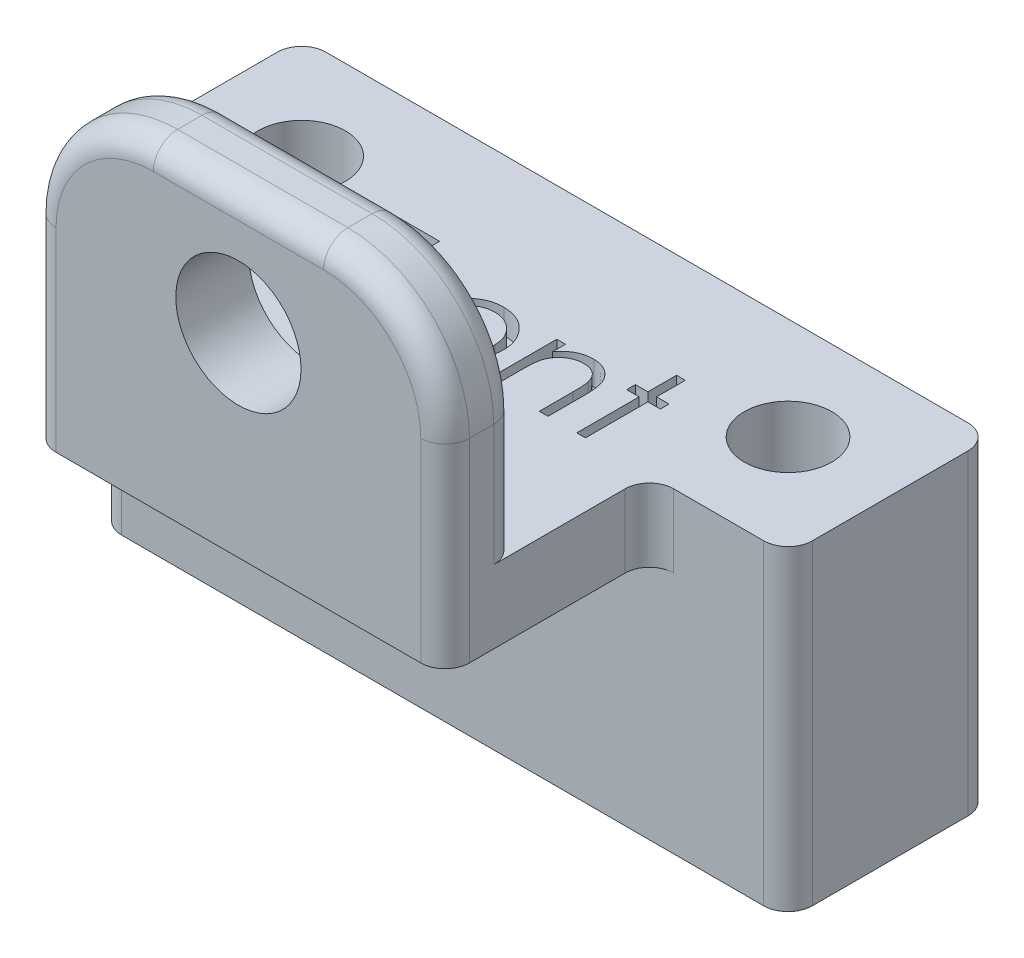
SolidWorks part; units mm, degrees
ref_plane "Front Plane" through (0, 0, 0) normal (0, 0, 1) x (1, 0, 0)
ref_plane "Top Plane" through (0, 0, 0) normal (0, 1, 0) x (1, 0, 0)
ref_plane "Right Plane" through (0, 0, 0) normal (1, 0, 0) x (0, 0, -1)
sketch "Sketch1" plane through (0, 0, 0) normal (1, 0, 0) x (0, 0, -1)
  line L0 (0, 0) -> (16.8, 0)
  line L1 (16.8, 0) -> (16.8, 3)
  line L2 (16.8, 3) -> (3, 3)
  line L3 (3, 3) -> (3, 13)
  line L4 (3, 13) -> (0, 13)
  line L5 (0, 13) -> (0, 0)
  line L6 (8.4, 3) -> (8.4, 0)
  dimension "D1" = 3
  dimension "D2" = 13
  dimension "D3" = 16.8
  dimension "D4" = 8.4
extrude "Boss-Extrude1" add sketch "Sketch1" along normal blind 17 contours L6 L2 L3 L4 L5 L0 | L2 L6 L0 L1 region at (0, 5.0326, -2.7326) region at (0, 1.5, -12.6)
extrude "Boss-Extrude3" add sketch "Sketch1<3>" against normal blind 5.7 from offset 0 contours L2 L6 L0 L1 region at (0, 1.5, -12.6)
sketch "Sketch1<3>" plane through (0, 0, 0) normal (1, 0, 0) x (0, 0, -1) same geometry as "Sketch1"
extrude "Boss-Extrude4" add sketch "Sketch1<4>" along normal blind 5.7 from surface contours L2 L6 L0 L1 region at (0, 1.5, -12.6) starting at face at (17, 5.3333, -6.6)
sketch "Sketch1<4>" plane through (0, 0, 0) normal (1, 0, 0) x (0, 0, -1) same geometry as "Sketch1"
sketch "Sketch2" plane through (0, 0, 0) normal (0, 0, 1) x (1, 0, 0)
  line L2 (8.5, 0) -> (8.5, 8) construction
  line L3 (17, 13) -> (0, 13) construction
  line L4 (17, 0) -> (0, 0) construction
  point P7 (8.5, 8)
  point P13 (8.5, 8)
  dimension "D1" = 5
hole_wizard "Ø5.0mm Dowel Hole1" positions "Sketch2" profile "Sketch3" hole size "Ø5.0" standard "ANSI Metric"
sketch "Sketch3" plane through (8.5, 8, 0) normal (1, 0, 0) x (0, -1, 0)
  line L0 (0, 0) -> (0, 4.5472)
  line L1 (0, 4.5472) -> (2.575, 3)
  line L2 (2.575, 3) -> (2.575, 0)
  line L5 (2.575, 0) -> (0, 0)
  line L10 (0, 4.5472) -> (-2.575, 3) construction
  line L11 (0, -6.35) -> (0, 107.95) construction
  dimension "Hole Dia." = 5.15
  dimension "Hole Depth" = 3
  dimension "Drill Angle" = 118
fillet "Fillet1" radius 5 2 edges at (0, 13, -1.5) (17, 13, -1.5)
sketch "Sketch4" plane through (0, 3, 0) normal (0, 1, 0) x (1, 0, 0)
  line L9 (-5.7, 12.6) -> (22.7, 12.6) construction
  line L10 (-5.7, 16.8) -> (-5.7, 8.4) construction
  line L11 (22.7, 8.4) -> (22.7, 16.8) construction
  line L13 (8.5, 12.6) -> (8.5, 16.8) construction
  line L14 (22.7, 16.8) -> (-5.7, 16.8) construction
  point P67 (-1.5, 12.6)
  point P76 (18.5, 12.6)
  dimension "D1" = 10
hole_wizard "M3 Clearance Hole1" positions "Sketch4" profile "Sketch5" hole size "M3" standard "ANSI Metric" end condition through all
sketch "Sketch5" plane through (18.5, 3, -12.6) normal (1, 0, 0) x (0, 0, 1)
  line L0 (0, 0) -> (0, 3)
  line L1 (0, 3) -> (1.8, 3)
  line L2 (1.8, 3) -> (1.8, 0)
  line L5 (1.8, 0) -> (0, 0)
  line L11 (0, -6.35) -> (0, 107.95) construction
  dimension "Thru Hole Dia." = 3.6
  dimension "Thru Hole Depth" = 3
fillet "Fillet2" radius 1 16 edges at (1.4645, 11.5355, 0) (8.5, 13, 0) (15.5355, 11.5355, 0) (0, 4, 0) (17, 4, 0) (22.7, 1.5, -16.8) (22.7, 1.5, -8.4) (-5.7, 1.5, -16.8) (0, 1.5, -8.4) (-5.7, 1.5, -8.4) (17, 5.5, -3) (15.5355, 11.5355, -3) (8.5, 13, -3) (1.4645, 11.5355, -3) (0, 5.5, -3) (17, 1.5, -8.4)
sketch "Sketch6" plane through (0, 0, 0) normal (0, -1, 0) x (1, 0, 0)
  line L0 (-1, -8.4) -> (18, -8.4)
  line L8 (16, 0) -> (1, 0)
  line L9 (0, -1) -> (0, -7.4)
  line L10 (-1, -8.4) -> (-4.7, -8.4)
  line L11 (-5.7, -9.4) -> (-5.7, -15.8)
  line L12 (-4.7, -16.8) -> (21.7, -16.8)
  line L13 (22.7, -15.8) -> (22.7, -9.4)
  line L14 (21.7, -8.4) -> (18, -8.4)
  line L15 (17, -7.4) -> (17, -1)
  line L16 (16, 0) -> (1, 0)
  line L17 (0, -1) -> (0, -7.4)
  line L18 (-1, -8.4) -> (-4.7, -8.4)
  line L19 (-5.7, -9.4) -> (-5.7, -15.8)
  line L20 (-4.7, -16.8) -> (21.7, -16.8)
  line L21 (22.7, -15.8) -> (22.7, -9.4)
  line L22 (21.7, -8.4) -> (18, -8.4)
  line L23 (17, -7.4) -> (17, -1)
  arc A7 (1, 0) -> (0, -1) centre (1, -1) ccw
  arc A8 (-1, -8.4) -> (0, -7.4) centre (-1, -7.4) ccw
  arc A9 (-4.7, -8.4) -> (-5.7, -9.4) centre (-4.7, -9.4) ccw
  arc A10 (-5.7, -15.8) -> (-4.7, -16.8) centre (-4.7, -15.8) ccw
  arc A11 (21.7, -16.8) -> (22.7, -15.8) centre (21.7, -15.8) ccw
  arc A12 (22.7, -9.4) -> (21.7, -8.4) centre (21.7, -9.4) ccw
  arc A13 (17, -1) -> (16, 0) centre (16, -1) ccw
  arc A14 (1, 0) -> (0, -1) centre (1, -1) ccw
  arc A15 (-1, -8.4) -> (0, -7.4) centre (-1, -7.4) ccw
  arc A16 (-4.7, -8.4) -> (-5.7, -9.4) centre (-4.7, -9.4) ccw
  arc A17 (-5.7, -15.8) -> (-4.7, -16.8) centre (-4.7, -15.8) ccw
  arc A18 (21.7, -16.8) -> (22.7, -15.8) centre (21.7, -15.8) ccw
  arc A19 (22.7, -9.4) -> (21.7, -8.4) centre (21.7, -9.4) ccw
  arc A20 (17, -1) -> (16, 0) centre (16, -1) ccw
  arc A22 (17, -7.4) -> (18, -8.4) centre (18, -7.4) ccw
  arc A23 (17, -7.4) -> (18, -8.4) centre (18, -7.4) ccw
  circle M16 centre (-1.5, -12.6) radius 1.8
  circle M17 centre (18.5, -12.6) radius 1.8
  line M22 (-1, -8.4) -> (-4.7, -8.4)
  arc M23 (-4.7, -8.4) -> (-5.7, -9.4) centre (-4.7, -9.4) ccw
  line M24 (-5.7, -9.4) -> (-5.7, -15.8)
  arc M25 (-5.7, -15.8) -> (-4.7, -16.8) centre (-4.7, -15.8) ccw
  line M26 (-4.7, -16.8) -> (21.7, -16.8)
  arc M27 (21.7, -16.8) -> (22.7, -15.8) centre (21.7, -15.8) ccw
  line M28 (22.7, -15.8) -> (22.7, -9.4)
  arc M29 (22.7, -9.4) -> (21.7, -8.4) centre (21.7, -9.4) ccw
  line M30 (21.7, -8.4) -> (18, -8.4)
  dimension "D1" = 0
extrude "Boss-Extrude5" add sketch "Sketch6" along normal blind 10 contours L0 M22 M23 M24 M25 M26 M27 M28 M29 M30 M17 M16 region at (8.5, 0, -12.6)
sketch "Sketch7" plane through (0, 3, 0) normal (0, 1, 0) x (1, 0, 0)
  line L0 (-2.85, 8.4) -> (19.85, 8.4) construction
  line L1 (-4.7, 8.4) -> (-1, 8.4) construction
  line L2 (21.7, 8.4) -> (18, 8.4) construction
  text T0 "Front" font "Century Gothic" height 4
  point P2 (0, 0)
extrude "Cut-Extrude1" cut sketch "Sketch7" against normal blind 1
sketch "Sketch8" [suppressed] plane through (0, 3, 0) normal (0, 1, 0) x (1, 0, 0)
  line L0 (-2.85, 5.4) -> (19.85, 5.4) construction
  line L1 (-4.7, 5.4) -> (-1, 5.4) construction
  line L2 (21.7, 5.4) -> (18, 5.4) construction
  text T0 "Rear" font "Century Gothic" height 4
extrude "Cut-Extrude2" [suppressed] cut sketch "Sketch8" against normal blind 1
equation "\"Length\" = 13.8 + 3"
equation "\"D3@Sketch1\"=\"Length\""
